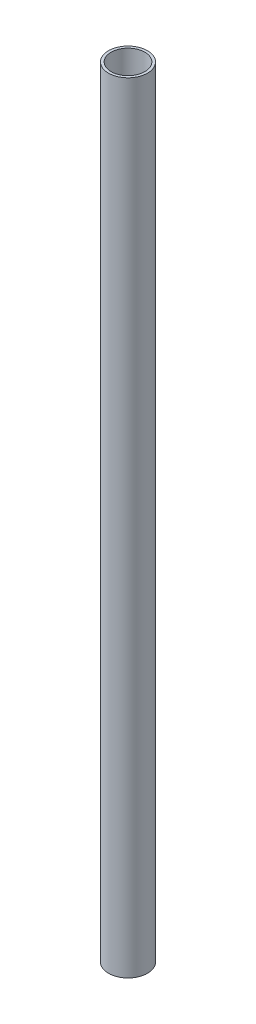
SolidWorks part; units mm, degrees
material "Thornel Mat VMA"
ref_plane "Front Plane" through (0, 0, 0) normal (0, 0, 1) x (1, 0, 0)
ref_plane "Top Plane" through (0, 0, 0) normal (0, 1, 0) x (1, 0, 0)
ref_plane "Right Plane" through (0, 0, 0) normal (1, 0, 0) x (0, 0, -1)
sketch "Sketch1" plane through (0, 0, 0) normal (0, 1, 0) x (1, 0, 0)
  circle A0 centre (0, 0) radius 15
  circle A1 centre (0, 0) radius 13
  dimension "D1" = 30
  dimension "D2" = 26
extrude "Boss-Extrude1" add sketch "Sketch1" along normal blind 600
